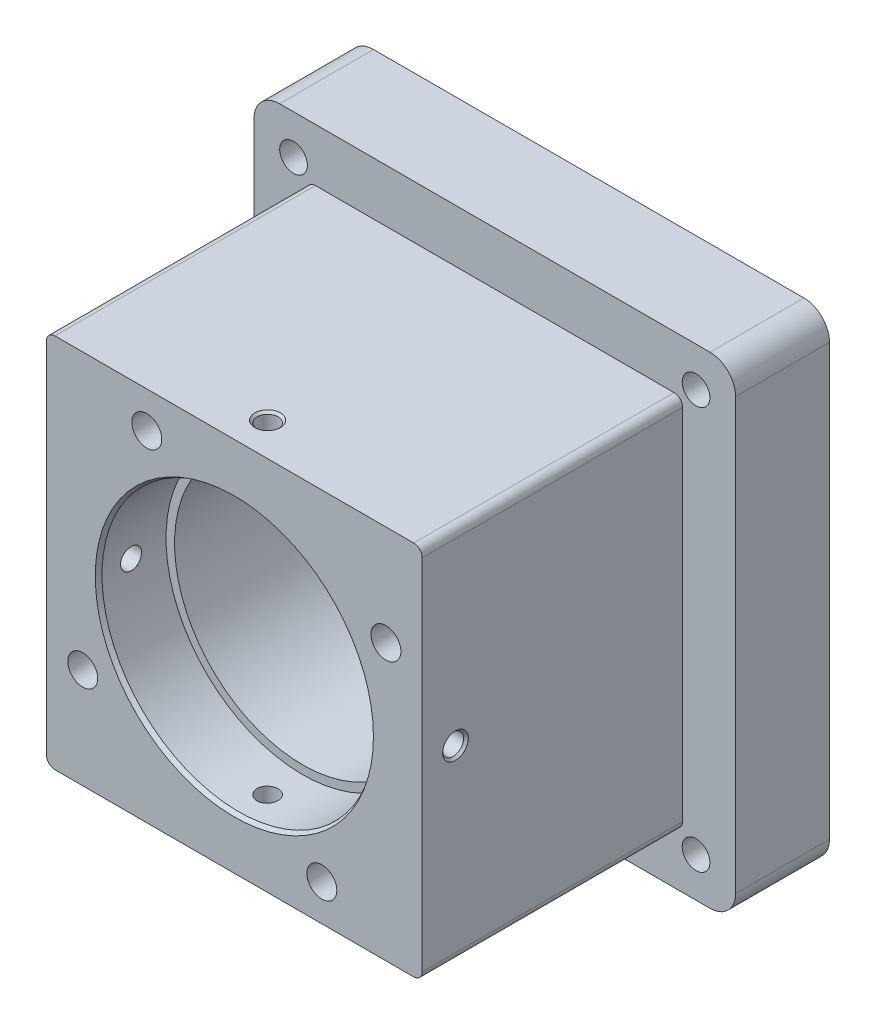
SolidWorks part; units mm, degrees
ref_plane "Front Plane" through (0, 0, 0) normal (0, 0, 1) x (1, 0, 0)
ref_plane "Top Plane" through (0, 0, 0) normal (0, 1, 0) x (1, 0, 0)
ref_plane "Right Plane" through (0, 0, 0) normal (1, 0, 0) x (0, 0, -1)
ref_plane "Plane1" through (0, 0, 0) normal (0, 0, 1) x (1, 0, 0)
sketch "Sketch1" plane through (0, 0, 0) normal (0, 0, 1) x (1, 0, 0)
  line L0 (-25.2, -28.2) -> (25.2, -28.2)
  line L1 (28.2, -25.2) -> (28.2, 25.2)
  line L2 (25.2, 28.2) -> (-25.2, 28.2)
  line L3 (-28.2, 25.2) -> (-28.2, -25.2)
  arc A0 (-28.2, -25.2) -> (-25.2, -28.2) centre (-25.2, -25.2) ccw
  arc A1 (25.2, -28.2) -> (28.2, -25.2) centre (25.2, -25.2) ccw
  arc A2 (28.2, 25.2) -> (25.2, 28.2) centre (25.2, 25.2) ccw
  arc A3 (-25.2, 28.2) -> (-28.2, 25.2) centre (-25.2, 25.2) ccw
extrude "Boss-Extrude1" add sketch "Sketch1" along normal blind 11
ref_plane "Plane2" through (0, 0, 41.5) normal (0, 0, 1) x (1, 0, 0)
sketch "Sketch2" plane through (0, 0, 0) normal (0, 0, 1) x (1, 0, 0)
  line L0 (-21, -22) -> (21, -22)
  line L1 (22, -21) -> (22, 21)
  line L2 (21, 22) -> (-21, 22)
  line L3 (-22, 21) -> (-22, -21)
  arc A0 (-22, -21) -> (-21, -22) centre (-21, -21) ccw
  arc A1 (21, -22) -> (22, -21) centre (21, -21) ccw
  arc A2 (22, 21) -> (21, 22) centre (21, 21) ccw
  arc A3 (-21, 22) -> (-22, 21) centre (-21, 21) ccw
extrude "Boss-Extrude2" add sketch "Sketch2" along normal blind 41.5
sketch "Sketch3" plane through (0, 0, 0) normal (1, 0, 0) x (0, 0, -1)
  line L0 (-41.5, 0) -> (-41.5, 16.2887)
  line L1 (-41.5, 16.2887) -> (-41, 16)
  line L2 (-41, 16) -> (-33.5, 16)
  line L3 (-33.5, 16) -> (-33.5, 15)
  line L4 (-33.5, 15) -> (-3, 15)
  line L5 (-3, 15) -> (-3, 19.065)
  line L6 (-3, 19.065) -> (-0.5, 19.065)
  line L7 (-0.5, 19.065) -> (0, 19.565)
  line L8 (0, 19.565) -> (0, 0)
  line L9 (0, 0) -> (-41.5, 0)
  line L10 (0, 0) -> (-41.5, 0) construction
revolve "Cut-Revolve1" cut sketch "Sketch3" angle 360 about L10 reverse direction yes
ref_plane "Plane3" through (0, 0, 41.5) normal (0, 0, 1) x (1, 0, 0)
sketch "Sketch4" plane through (0, 0, 41.5) normal (0, 0, 1) x (1, 0, 0)
  circle A0 centre (17.7535, 10.25) radius 1.75
extrude "Cut-Extrude1" cut sketch "Sketch4" against normal blind 3.5
sketch "Sketch5" plane through (0, 0, 41.5) normal (0, 0, 1) x (1, 0, 0)
  line L0 (17.7535, 10.25) -> (-10.25, 17.7535)
  line L1 (17.7535, 10.25) -> (10.25, -17.7535)
pattern_linear "LPattern1" count 2 spacing 28.9914 along (-0.9659, 0.2588, 0) count 2 spacing 28.9914 along (-0.2588, -0.9659, 0) of "Cut-Extrude1"
ref_plane "Plane4" through (23.57, 0, 0) normal (1, 0, 0) x (0, 0, -1)
ref_plane "Plane5" through (0, 0, 0) normal (0.7071, -0.7071, 0) x (-0.7071, -0.7071, 0)
sketch "Sketch6" plane through (23.57, 0, 0) normal (1, 0, 0) x (0, 0, -1)
  line L0 (-11.9359, 23.57) -> (-11, 25.191)
  line L1 (-11, 25.191) -> (-0.379, 25.191)
  line L2 (-0.379, 25.191) -> (0, 25.57)
  line L3 (0, 25.57) -> (0, 23.57)
  line L4 (0, 23.57) -> (-11.9359, 23.57)
  line L5 (0, 23.57) -> (-11.9359, 23.57) construction
revolve "Cut-Revolve2" cut sketch "Sketch6" angle 360 about L5 reverse direction yes
cosmetic thread "Cosmetic Thread1" parameters "D1"=11, "D2"=4
sketch "Sketch7" plane through (0, 0, 0) normal (0, 0, 1) x (1, 0, 0)
  line L0 (23.57, 23.57) -> (-23.57, 23.57)
  line L1 (23.57, 23.57) -> (23.57, -23.57)
pattern_linear "LPattern2" count 2 spacing 47.14 along (-1, 0, 0) count 2 spacing 47.14 along (0, -1, 0) of "Cut-Revolve2"
cosmetic thread "Cosmetic Thread2" parameters "D1"=11, "D2"=4
cosmetic thread "Cosmetic Thread3" parameters "D1"=11, "D2"=4
cosmetic thread "Cosmetic Thread4" parameters "D1"=11, "D2"=4
ref_plane "Plane6" through (0, 0, 37.6) normal (0, 0, 1) x (1, 0, 0)
sketch "Sketch8" plane through (0, 0, 37.6) normal (0, 0, 1) x (1, 0, 0)
  line L0 (-22, 0) -> (-22, 1.5)
  line L1 (-22, 1.5) -> (-21.7295, 1.2295)
  line L2 (-21.7295, 1.2295) -> (-15.8, 1.2295)
  line L3 (-15.8, 1.2295) -> (-15.8, 0)
  line L4 (-15.8, 0) -> (-22, 0)
  line L5 (-15.8, 0) -> (-22, 0) construction
revolve "Cut-Revolve3" cut sketch "Sketch8" angle 360 about L5 reverse direction yes
cosmetic thread "Cosmetic Thread5" parameters "D1"=5, "D2"=3
sketch "Sketch9" plane through (0, 0, 37.6) normal (0, 0, 1) x (1, 0, 0)
  line L0 (0, -22) -> (-1.5, -22)
  line L1 (-1.5, -22) -> (-1.2295, -21.7295)
  line L2 (-1.2295, -21.7295) -> (-1.2295, -15.8)
  line L3 (-1.2295, -15.8) -> (0, -15.8)
  line L4 (0, -15.8) -> (0, -22)
  line L5 (0, -15.8) -> (0, -22) construction
revolve "Cut-Revolve4" cut sketch "Sketch9" angle 360 about L5 reverse direction yes
cosmetic thread "Cosmetic Thread6" parameters "D1"=5, "D2"=3
sketch "Sketch10" plane through (0, 0, 37.6) normal (0, 0, 1) x (1, 0, 0)
  line L0 (22, 0) -> (22, -1.5)
  line L1 (22, -1.5) -> (21.7295, -1.2295)
  line L2 (21.7295, -1.2295) -> (15.8, -1.2295)
  line L3 (15.8, -1.2295) -> (15.8, 0)
  line L4 (15.8, 0) -> (22, 0)
  line L5 (15.8, 0) -> (22, 0) construction
revolve "Cut-Revolve5" cut sketch "Sketch10" angle 360 about L5 reverse direction yes
cosmetic thread "Cosmetic Thread7" parameters "D1"=5, "D2"=3
sketch "Sketch11" plane through (0, 0, 37.6) normal (0, 0, 1) x (1, 0, 0)
  line L0 (0, 22) -> (1.5, 22)
  line L1 (1.5, 22) -> (1.2295, 21.7295)
  line L2 (1.2295, 21.7295) -> (1.2295, 15.8)
  line L3 (1.2295, 15.8) -> (0, 15.8)
  line L4 (0, 15.8) -> (0, 22)
  line L5 (0, 15.8) -> (0, 22) construction
revolve "Cut-Revolve6" cut sketch "Sketch11" angle 360 about L5 reverse direction yes
cosmetic thread "Cosmetic Thread8" parameters "D1"=5, "D2"=3
ref_plane "Plane7" through (0, 0, 11) normal (0, 0, 1) x (1, 0, 0)
ref_plane "Plane8" through (22, 0, 0) normal (1, 0, 0) x (0, 0, -1)
ref_plane "Plane9" through (-22, 0, 0) normal (1, 0, 0) x (0, 0, -1)
ref_plane "Plane10" through (0, -22, 0) normal (0, 1, 0) x (1, 0, 0)
ref_plane "Plane11" through (0, 22, 0) normal (0, 1, 0) x (1, 0, 0)
ref_plane "Plane12" through (0, 0, -5) normal (0, 0, 1) x (1, 0, 0)
ref_plane "Plane13" through (0, 0, -5) normal (0, 0, 1) x (1, 0, 0)
ref_plane "Plane14" through (0, 0, 13.8) normal (0, 0, 1) x (1, 0, 0)
ref_plane "Plane15" through (0, 0, 41.5) normal (0, 0, 1) x (1, 0, 0)
ref_plane "ANBAU XY" through (0, 0, 0) normal (0, 0, 1) x (1, 0, 0)
ref_plane "ANBAU XZ" through (0, 0, 0) normal (0, 1, 0) x (1, 0, 0)
ref_plane "ANBAU YZ" through (0, 0, 0) normal (-1, 0, 0) x (0, 0, 1)
ref_axis "ANBAU X" through (80.9, 0, 0) along (-1, 0, 0)
ref_axis "ANBAU Y" through (0, 50, 0) along (0, -1, 0)
ref_axis "ANBAU Z" through (0, 0, 80.9) along (0, 0, -1)
sketch3d "ANBAU"
  point P0 (0, 0, 0)
ref_plane "ANBAU_HGO XY" through (0, 0, 41.5) normal (0, 0, 1) x (1, 0, 0)
ref_plane "ANBAU_HGO XZ" through (0, 0, 0) normal (0, -1, 0) x (-1, 0, 0)
ref_plane "ANBAU_HGO YZ" through (0, 0, 0) normal (1, 0, 0) x (0, 0, -1)
ref_axis "ANBAU_HGO X" through (-80.9, 0, 41.5) along (1, 0, 0)
ref_axis "ANBAU_HGO Y" through (0, -50, 41.5) along (0, 1, 0)
ref_axis "ANBAU_HGO Z" through (0, 0, 80.9) along (0, 0, -1)
sketch3d "ANBAU_HGO"
  point P0 (0, 0, 41.5)
ref_plane "IP1 XY" through (0, 0, 0) normal (0, 0, -1) x (-1, 0, 0)
ref_plane "IP1 XZ" through (0, 0, 0) normal (1, 0, 0) x (0, 0, -1)
ref_plane "IP1 YZ" through (0, 0, 0) normal (0, -1, 0) x (-1, 0, 0)
ref_axis "IP1 X" through (0, 50, 0) along (0, -1, 0)
ref_axis "IP1 Y" through (80.9, 0, 0) along (-1, 0, 0)
ref_axis "IP1 Z" through (0, 0, -50) along (0, 0, 1)
sketch3d "IP1"
  point P0 (0, 0, 0)
ref_plane "to_nabe XY" through (0, 0, 13.8) normal (0, 0, 1) x (1, 0, 0)
ref_plane "to_nabe XZ" through (0, 0, 0) normal (0, -1, 0) x (-1, 0, 0)
ref_plane "to_nabe YZ" through (0, 0, 0) normal (1, 0, 0) x (0, 0, -1)
ref_axis "to_nabe X" through (-80.9, 0, 13.8) along (1, 0, 0)
ref_axis "to_nabe Y" through (0, -50, 13.8) along (0, 1, 0)
ref_axis "to_nabe Z" through (0, 0, 80.9) along (0, 0, -1)
sketch3d "to_nabe"
  point P0 (0, 0, 13.8)
ref_plane "to_screwsA 1 XY" through (0, 0, 11) normal (0, 0, 1) x (1, 0, 0)
ref_plane "to_screwsA 1 XZ" through (0, 23.57, 0) normal (0, -1, 0) x (-1, 0, 0)
ref_plane "to_screwsA 1 YZ" through (23.57, 0, 0) normal (1, 0, 0) x (0, 0, -1)
ref_axis "to_screwsA 1 X" through (-80.9, 23.57, 11) along (1, 0, 0)
ref_axis "to_screwsA 1 Y" through (23.57, -50, 11) along (0, 1, 0)
ref_axis "to_screwsA 1 Z" through (23.57, 23.57, 80.9) along (0, 0, -1)
sketch3d "to_screwsA 1"
  point P0 (23.57, 23.57, 11)
ref_plane "to_screwsA 2 XY" through (0, 0, 11) normal (0, 0, 1) x (1, 0, 0)
ref_plane "to_screwsA 2 XZ" through (0, 23.57, 0) normal (0, -1, 0) x (-1, 0, 0)
ref_plane "to_screwsA 2 YZ" through (-23.57, 0, 0) normal (1, 0, 0) x (0, 0, -1)
ref_axis "to_screwsA 2 X" through (-80.9, 23.57, 11) along (1, 0, 0)
ref_axis "to_screwsA 2 Y" through (-23.57, -50, 11) along (0, 1, 0)
ref_axis "to_screwsA 2 Z" through (-23.57, 23.57, 80.9) along (0, 0, -1)
sketch3d "to_screwsA 2"
  point P0 (-23.57, 23.57, 11)
ref_plane "to_screwsA 3 XY" through (0, 0, 11) normal (0, 0, 1) x (1, 0, 0)
ref_plane "to_screwsA 3 XZ" through (0, -23.57, 0) normal (0, -1, 0) x (-1, 0, 0)
ref_plane "to_screwsA 3 YZ" through (-23.57, 0, 0) normal (1, 0, 0) x (0, 0, -1)
ref_axis "to_screwsA 3 X" through (-80.9, -23.57, 11) along (1, 0, 0)
ref_axis "to_screwsA 3 Y" through (-23.57, -50, 11) along (0, 1, 0)
ref_axis "to_screwsA 3 Z" through (-23.57, -23.57, 80.9) along (0, 0, -1)
sketch3d "to_screwsA 3"
  point P0 (-23.57, -23.57, 11)
ref_plane "to_screwsA 4 XY" through (0, 0, 11) normal (0, 0, 1) x (1, 0, 0)
ref_plane "to_screwsA 4 XZ" through (0, -23.57, 0) normal (0, -1, 0) x (-1, 0, 0)
ref_plane "to_screwsA 4 YZ" through (23.57, 0, 0) normal (1, 0, 0) x (0, 0, -1)
ref_axis "to_screwsA 4 X" through (-80.9, -23.57, 11) along (1, 0, 0)
ref_axis "to_screwsA 4 Y" through (23.57, -50, 11) along (0, 1, 0)
ref_axis "to_screwsA 4 Z" through (23.57, -23.57, 80.9) along (0, 0, -1)
sketch3d "to_screwsA 4"
  point P0 (23.57, -23.57, 11)
ref_plane "to_screwsB 1 XY" through (0, 0, -5) normal (0, 0, -1) x (-1, 0, 0)
ref_plane "to_screwsB 1 XZ" through (0, 0, 0) normal (0, 1, 0) x (1, 0, 0)
ref_plane "to_screwsB 1 YZ" through (0, 0, 0) normal (1, 0, 0) x (0, 0, -1)
ref_axis "to_screwsB 1 X" through (-80.9, 0, -5) along (1, 0, 0)
ref_axis "to_screwsB 1 Y" through (0, 50, -5) along (0, -1, 0)
ref_axis "to_screwsB 1 Z" through (0, 0, -80.9) along (0, 0, 1)
sketch3d "to_screwsB 1"
  point P0 (0, 0, -5)
ref_plane "to_screwsB 2 XY" through (0, 0, -5) normal (0, 0, -1) x (-1, 0, 0)
ref_plane "to_screwsB 2 XZ" through (0, 0, 0) normal (0, 1, 0) x (1, 0, 0)
ref_plane "to_screwsB 2 YZ" through (0, 0, 0) normal (1, 0, 0) x (0, 0, -1)
ref_axis "to_screwsB 2 X" through (-80.9, 0, -5) along (1, 0, 0)
ref_axis "to_screwsB 2 Y" through (0, 50, -5) along (0, -1, 0)
ref_axis "to_screwsB 2 Z" through (0, 0, -80.9) along (0, 0, 1)
sketch3d "to_screwsB 2"
  point P0 (0, 0, -5)
ref_plane "to_screwsB 3 XY" through (0, 0, -5) normal (0, 0, -1) x (-1, 0, 0)
ref_plane "to_screwsB 3 XZ" through (0, 0, 0) normal (0, 1, 0) x (1, 0, 0)
ref_plane "to_screwsB 3 YZ" through (0, 0, 0) normal (1, 0, 0) x (0, 0, -1)
ref_axis "to_screwsB 3 X" through (-80.9, 0, -5) along (1, 0, 0)
ref_axis "to_screwsB 3 Y" through (0, 50, -5) along (0, -1, 0)
ref_axis "to_screwsB 3 Z" through (0, 0, -80.9) along (0, 0, 1)
sketch3d "to_screwsB 3"
  point P0 (0, 0, -5)
ref_plane "to_screwsB 4 XY" through (0, 0, -5) normal (0, 0, -1) x (-1, 0, 0)
ref_plane "to_screwsB 4 XZ" through (0, 0, 0) normal (0, 1, 0) x (1, 0, 0)
ref_plane "to_screwsB 4 YZ" through (0, 0, 0) normal (1, 0, 0) x (0, 0, -1)
ref_axis "to_screwsB 4 X" through (-80.9, 0, -5) along (1, 0, 0)
ref_axis "to_screwsB 4 Y" through (0, 50, -5) along (0, -1, 0)
ref_axis "to_screwsB 4 Z" through (0, 0, -80.9) along (0, 0, 1)
sketch3d "to_screwsB 4"
  point P0 (0, 0, -5)
ref_plane "to_screwsC 1 XY" through (0, 0, 41.5) normal (0, 0, 1) x (1, 0, 0)
ref_plane "to_screwsC 1 XZ" through (0, 0, 0) normal (0, -1, 0) x (-1, 0, 0)
ref_plane "to_screwsC 1 YZ" through (0, 0, 0) normal (1, 0, 0) x (0, 0, -1)
ref_axis "to_screwsC 1 X" through (-80.9, 0, 41.5) along (1, 0, 0)
ref_axis "to_screwsC 1 Y" through (0, -50, 41.5) along (0, 1, 0)
ref_axis "to_screwsC 1 Z" through (0, 0, 80.9) along (0, 0, -1)
sketch3d "to_screwsC 1"
  point P0 (0, 0, 41.5)
ref_plane "to_screwsC 2 XY" through (0, 0, 41.5) normal (0, 0, 1) x (1, 0, 0)
ref_plane "to_screwsC 2 XZ" through (0, 0, 0) normal (0, -1, 0) x (-1, 0, 0)
ref_plane "to_screwsC 2 YZ" through (0, 0, 0) normal (1, 0, 0) x (0, 0, -1)
ref_axis "to_screwsC 2 X" through (-80.9, 0, 41.5) along (1, 0, 0)
ref_axis "to_screwsC 2 Y" through (0, -50, 41.5) along (0, 1, 0)
ref_axis "to_screwsC 2 Z" through (0, 0, 80.9) along (0, 0, -1)
sketch3d "to_screwsC 2"
  point P0 (0, 0, 41.5)
ref_plane "to_screwsC 3 XY" through (0, 0, 41.5) normal (0, 0, 1) x (1, 0, 0)
ref_plane "to_screwsC 3 XZ" through (0, 0, 0) normal (0, -1, 0) x (-1, 0, 0)
ref_plane "to_screwsC 3 YZ" through (0, 0, 0) normal (1, 0, 0) x (0, 0, -1)
ref_axis "to_screwsC 3 X" through (-80.9, 0, 41.5) along (1, 0, 0)
ref_axis "to_screwsC 3 Y" through (0, -50, 41.5) along (0, 1, 0)
ref_axis "to_screwsC 3 Z" through (0, 0, 80.9) along (0, 0, -1)
sketch3d "to_screwsC 3"
  point P0 (0, 0, 41.5)
ref_plane "to_screwsC 4 XY" through (0, 0, 41.5) normal (0, 0, 1) x (1, 0, 0)
ref_plane "to_screwsC 4 XZ" through (0, 0, 0) normal (0, -1, 0) x (-1, 0, 0)
ref_plane "to_screwsC 4 YZ" through (0, 0, 0) normal (1, 0, 0) x (0, 0, -1)
ref_axis "to_screwsC 4 X" through (-80.9, 0, 41.5) along (1, 0, 0)
ref_axis "to_screwsC 4 Y" through (0, -50, 41.5) along (0, 1, 0)
ref_axis "to_screwsC 4 Z" through (0, 0, 80.9) along (0, 0, -1)
sketch3d "to_screwsC 4"
  point P0 (0, 0, 41.5)
ref_plane "to_screwsD 1 XY" through (0, 0, -5) normal (0, 0, -1) x (-1, 0, 0)
ref_plane "to_screwsD 1 XZ" through (0, 23.57, 0) normal (0, 1, 0) x (1, 0, 0)
ref_plane "to_screwsD 1 YZ" through (23.57, 0, 0) normal (1, 0, 0) x (0, 0, -1)
ref_axis "to_screwsD 1 X" through (-80.9, 23.57, -5) along (1, 0, 0)
ref_axis "to_screwsD 1 Y" through (23.57, 50, -5) along (0, -1, 0)
ref_axis "to_screwsD 1 Z" through (23.57, 23.57, -80.9) along (0, 0, 1)
sketch3d "to_screwsD 1"
  point P0 (23.57, 23.57, -5)
ref_plane "to_screwsD 2 XY" through (0, 0, -5) normal (0, 0, -1) x (-1, 0, 0)
ref_plane "to_screwsD 2 XZ" through (0, 23.57, 0) normal (0, 1, 0) x (1, 0, 0)
ref_plane "to_screwsD 2 YZ" through (-23.57, 0, 0) normal (1, 0, 0) x (0, 0, -1)
ref_axis "to_screwsD 2 X" through (-80.9, 23.57, -5) along (1, 0, 0)
ref_axis "to_screwsD 2 Y" through (-23.57, 50, -5) along (0, -1, 0)
ref_axis "to_screwsD 2 Z" through (-23.57, 23.57, -80.9) along (0, 0, 1)
sketch3d "to_screwsD 2"
  point P0 (-23.57, 23.57, -5)
ref_plane "to_screwsD 3 XY" through (0, 0, -5) normal (0, 0, -1) x (-1, 0, 0)
ref_plane "to_screwsD 3 XZ" through (0, -23.57, 0) normal (0, 1, 0) x (1, 0, 0)
ref_plane "to_screwsD 3 YZ" through (-23.57, 0, 0) normal (1, 0, 0) x (0, 0, -1)
ref_axis "to_screwsD 3 X" through (-80.9, -23.57, -5) along (1, 0, 0)
ref_axis "to_screwsD 3 Y" through (-23.57, 50, -5) along (0, -1, 0)
ref_axis "to_screwsD 3 Z" through (-23.57, -23.57, -80.9) along (0, 0, 1)
sketch3d "to_screwsD 3"
  point P0 (-23.57, -23.57, -5)
ref_plane "to_screwsD 4 XY" through (0, 0, -5) normal (0, 0, -1) x (-1, 0, 0)
ref_plane "to_screwsD 4 XZ" through (0, -23.57, 0) normal (0, 1, 0) x (1, 0, 0)
ref_plane "to_screwsD 4 YZ" through (23.57, 0, 0) normal (1, 0, 0) x (0, 0, -1)
ref_axis "to_screwsD 4 X" through (-80.9, -23.57, -5) along (1, 0, 0)
ref_axis "to_screwsD 4 Y" through (23.57, 50, -5) along (0, -1, 0)
ref_axis "to_screwsD 4 Z" through (23.57, -23.57, -80.9) along (0, 0, 1)
sketch3d "to_screwsD 4"
  point P0 (23.57, -23.57, -5)
ref_plane "to_stift_A1 XY" through (22, 0, 0) normal (1, 0, 0) x (0, 0, -1)
ref_plane "to_stift_A1 XZ" through (0, 0, 0) normal (0, -1, 0) x (-1, 0, 0)
ref_plane "to_stift_A1 YZ" through (0, 0, 37.6) normal (0, 0, -1) x (-1, 0, 0)
ref_axis "to_stift_A1 X" through (22, 0, 80.9) along (0, 0, -1)
ref_axis "to_stift_A1 Y" through (22, -50, 37.6) along (0, 1, 0)
ref_axis "to_stift_A1 Z" through (80.9, 0, 37.6) along (-1, 0, 0)
sketch3d "to_stift_A1"
  point P0 (22, 0, 37.6)
ref_plane "to_stift_A1_1 XY" through (0, -22, 0) normal (0, -1, 0) x (-1, 0, 0)
ref_plane "to_stift_A1_1 XZ" through (0, 0, 37.6) normal (0, 0, -1) x (-1, 0, 0)
ref_plane "to_stift_A1_1 YZ" through (0, 0, 0) normal (1, 0, 0) x (0, 0, -1)
ref_axis "to_stift_A1_1 X" through (-80.9, -22, 37.6) along (1, 0, 0)
ref_axis "to_stift_A1_1 Y" through (0, -22, -50) along (0, 0, 1)
ref_axis "to_stift_A1_1 Z" through (0, -50, 37.6) along (0, 1, 0)
sketch3d "to_stift_A1_1"
  point P0 (0, -22, 37.6)
ref_plane "to_stift_A1_2 XY" through (0, 22, 0) normal (0, 1, 0) x (1, 0, 0)
ref_plane "to_stift_A1_2 XZ" through (0, 0, 37.6) normal (0, 0, 1) x (1, 0, 0)
ref_plane "to_stift_A1_2 YZ" through (0, 0, 0) normal (1, 0, 0) x (0, 0, -1)
ref_axis "to_stift_A1_2 X" through (-80.9, 22, 37.6) along (1, 0, 0)
ref_axis "to_stift_A1_2 Y" through (0, 22, 50) along (0, 0, -1)
ref_axis "to_stift_A1_2 Z" through (0, 50, 37.6) along (0, -1, 0)
sketch3d "to_stift_A1_2"
  point P0 (0, 22, 37.6)
ref_plane "to_stift_A2 XY" through (-22, 0, 0) normal (-1, 0, 0) x (0, 0, 1)
ref_plane "to_stift_A2 XZ" through (0, 0, 0) normal (0, 1, 0) x (1, 0, 0)
ref_plane "to_stift_A2 YZ" through (0, 0, 37.6) normal (0, 0, -1) x (-1, 0, 0)
ref_axis "to_stift_A2 X" through (-22, 0, 80.9) along (0, 0, -1)
ref_axis "to_stift_A2 Y" through (-22, 50, 37.6) along (0, -1, 0)
ref_axis "to_stift_A2 Z" through (-80.9, 0, 37.6) along (1, 0, 0)
sketch3d "to_stift_A2"
  point P0 (-22, 0, 37.6)
other "Freeze***"
